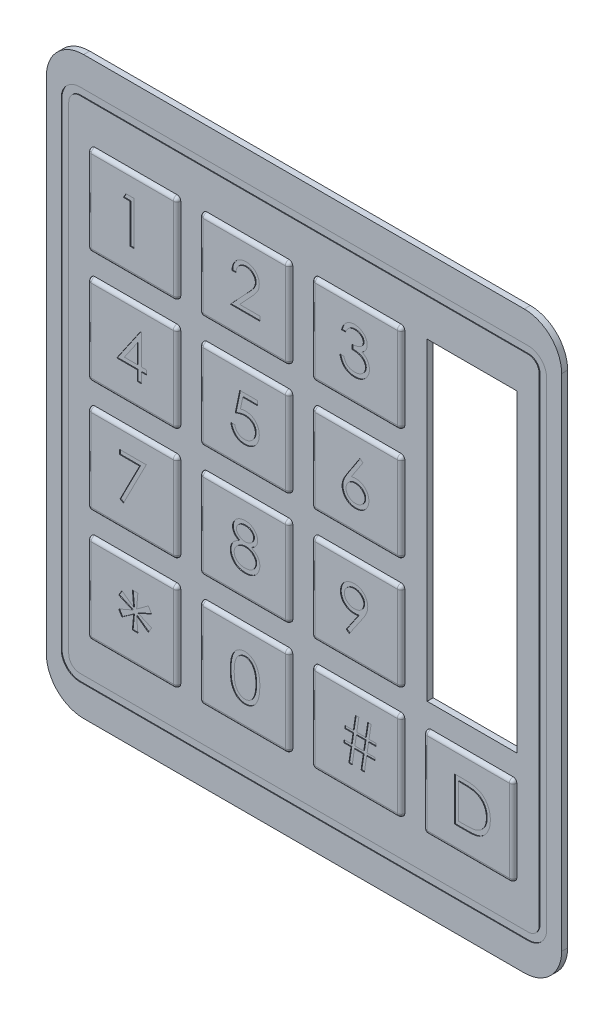
SolidWorks part; units mm, degrees
ref_plane "Alzado" through (0, 0, 0) normal (0, 0, 1) x (1, 0, 0)
ref_plane "Planta" through (0, 0, 0) normal (0, 1, 0) x (1, 0, 0)
ref_plane "Vista lateral" through (0, 0, 0) normal (1, 0, 0) x (0, 0, -1)
sketch "Croquis1" plane through (0, 0, 0) normal (0, 0, 1) x (1, 0, 0)
  line L1 (-34.5, 38.5) -> (34.5, 38.5)
  line L2 (-34.5, 38.5) -> (-34.5, -38.5)
  line L3 (-34.5, -38.5) -> (34.5, -38.5)
  line L4 (34.5, 38.5) -> (34.5, -38.5)
  point P4 (0, 38.5)
  point P6 (-34.5, 0)
  dimension "D1" = 77
  dimension "D2" = 69
extrude "Saliente-Extruir1" add sketch "Croquis1" along normal blind 0.81
fillet "Redondeo1" radius 5 4 edges at (-34.5, -38.5, 0.405) (34.5, -38.5, 0.405) (-34.5, 38.5, 0.405) (34.5, 38.5, 0.405)
sketch "Croquis4" plane through (0, 0, 0.81) normal (0, 0, 1) x (1, 0, 0)
  line L0 (-34.5, 33.5) -> (-34.5, -33.5) construction
  line L1 (-28.5, 28.5) -> (-16.5, 28.5)
  line L2 (-28.5, 28.5) -> (-28.5, 16.5)
  line L3 (-28.5, 16.5) -> (-16.5, 16.5)
  line L4 (-16.5, 28.5) -> (-16.5, 16.5)
  line L5 (29.5, 38.5) -> (-29.5, 38.5) construction
  dimension "D1" = 12
  dimension "D2" = 6
  dimension "D3" = 10
extrude "Saliente-Extruir2" add sketch "Croquis4" along normal blind 0.5
fillet "Redondeo2" radius 0.5 4 edges at (-22.5, 28.5, 1.31) (-16.5, 22.5, 1.31) (-22.5, 16.5, 1.31) (-28.5, 22.5, 1.31)
pattern_linear "MatrizL1" count 4 spacing 15 along (1, 0, 0) count 4 spacing 15 along (0, -1, 0) of "Saliente-Extruir2", "Redondeo2"
sketch "Croquis5" plane through (0, 0, 0.81) normal (0, 0, 1) x (1, 0, 0)
  line L0 (-34.5, 33.5) -> (-34.5, -33.5) construction
  line L1 (-30, 34.5) -> (30, 34.5)
  line L2 (-32.5, 32) -> (-32.5, -32)
  line L3 (-30, -34.5) -> (30, -34.5)
  line L4 (32.5, 32) -> (32.5, -32)
  line L5 (34.5, -33.5) -> (34.5, 33.5) construction
  line L6 (29.5, 38.5) -> (-29.5, 38.5) construction
  line L7 (-29.5, -38.5) -> (29.5, -38.5) construction
  line L8 (-30, 33.5) -> (30, 33.5)
  line L9 (31.5, 32) -> (31.5, -32)
  line L10 (-30, -33.5) -> (30, -33.5)
  line L11 (-31.5, 32) -> (-31.5, -32)
  arc A0 (-32.5, -32) -> (-30, -34.5) centre (-30, -32) ccw
  arc A1 (32.5, -32) -> (30, -34.5) centre (30, -32) cw
  arc A2 (32.5, 32) -> (30, 34.5) centre (30, 32) ccw
  arc A3 (-30, 34.5) -> (-32.5, 32) centre (-30, 32) ccw
  arc A4 (31.5, 32) -> (30, 33.5) centre (30, 32) ccw
  arc A5 (31.5, -32) -> (30, -33.5) centre (30, -32) cw
  arc A6 (-31.5, -32) -> (-30, -33.5) centre (-30, -32) ccw
  arc A7 (-30, 33.5) -> (-31.5, 32) centre (-30, 32) ccw
  dimension "D5" = 2.5
  dimension "D1" = 2
  dimension "D2" = 2
  dimension "D3" = 4
  dimension "D4" = 4
  dimension "D6" = 1
extrude "Cortar-Extruir1" cut sketch "Croquis5" against normal blind 0.1
sketch "Croquis6" plane through (0, 0, 1.31) normal (0, 0, 1) x (1, 0, 0)
  text T0 "1" font "Century Gothic" height in points 22
  text T1 "2" font "Century Gothic" height in points 22
  text T2 "3" font "Century Gothic" height in points 22
  text T3 "A" font "Century Gothic" height in points 22
  text T4 "B" font "Century Gothic" height in points 22
  text T5 "C" font "Century Gothic" height in points 22
  text T6 "D" font "Century Gothic" height in points 22
  text T7 "#" font "Century Gothic" height in points 22
  text T8 "0" font "Century Gothic" height in points 22
  text T9 "*" font "Century Gothic" height in points 36
  text T10 "4" font "Century Gothic" height in points 22
  text T11 "5" font "Century Gothic" height in points 22
  text T12 "6" font "Century Gothic" height in points 22
  text T13 "7" font "Century Gothic" height in points 22
  text T14 "8" font "Century Gothic" height in points 22
  text T15 "9" font "Century Gothic" height in points 22
extrude "Cortar-Extruir2" cut sketch "Croquis6" against normal blind 0.1
sketch "Croquis7" plane through (0, 0, 0.81) normal (0, 0, 1) x (1, 0, 0)
  line L0 (16.5, 28.5) -> (16.5, -13.5)
  line L1 (16.5, -13.5) -> (28.5, -13.5)
  line L2 (28.5, -13.5) -> (28.5, 28.5)
  line L3 (28.5, 28.5) -> (16.5, 28.5)
extrude "Cortar-Extruir3" cut sketch "Croquis7" along normal through all both and the other way through all
